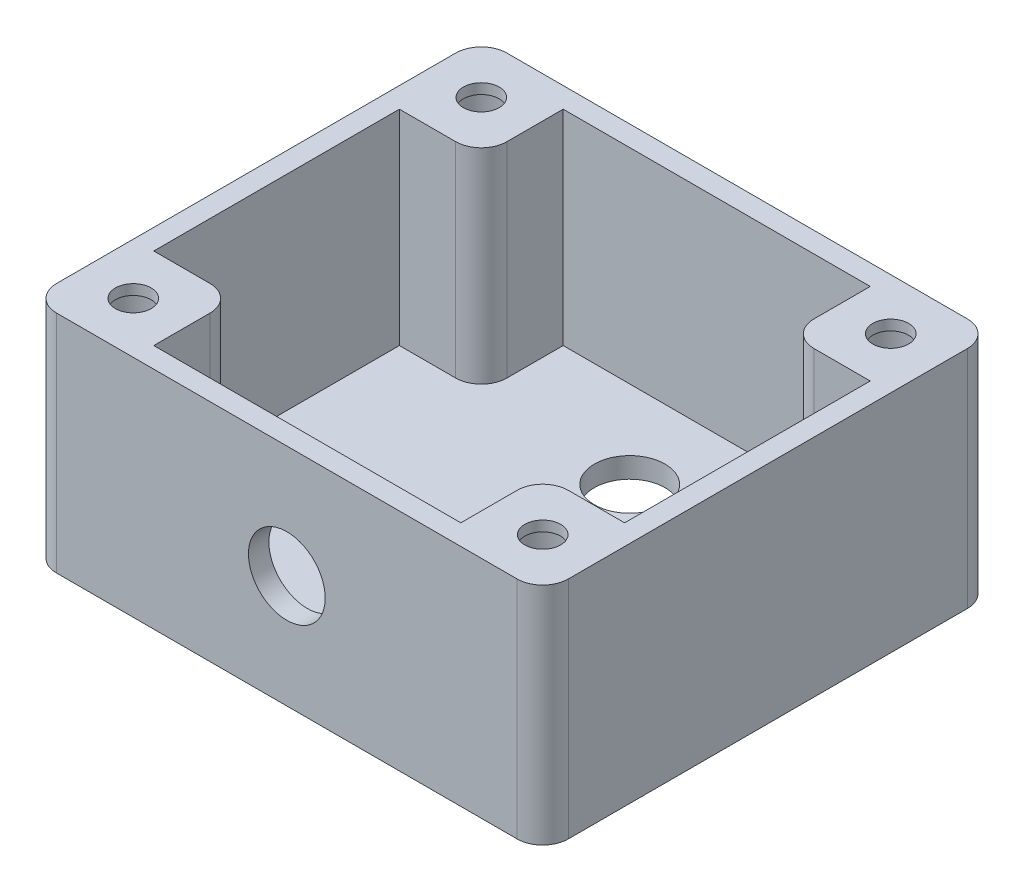
SolidWorks part; units mm, degrees
ref_plane "Front" through (0, 0, 0) normal (0, 0, 1) x (1, 0, 0)
ref_plane "Top" through (0, 0, 0) normal (0, 1, 0) x (1, 0, 0)
ref_plane "Right" through (0, 0, 0) normal (1, 0, 0) x (0, 0, -1)
sketch "Sketch1" plane through (0, 0, 0) normal (0, 1, 0) x (1, 0, 0)
  line L1 (-15, -20) -> (15, -20)
  line L2 (-15, -20) -> (-15, 20)
  line L3 (-15, 20) -> (15, 20)
  line L4 (15, -20) -> (15, 20)
  line L5 (-15, -20) -> (15, 20) construction
  line L6 (-15, 20) -> (15, -20) construction
  line L7 (-25, -22) -> (25, -22)
  line L8 (-25, -22) -> (-25, 22)
  line L9 (-25, 22) -> (25, 22)
  line L10 (25, -22) -> (25, 22)
  line L11 (-25, -22) -> (25, 22) construction
  line L12 (-25, 22) -> (25, -22) construction
  point P0 (0, 0)
  point P6 (0, 0)
  point P7 (0, 0)
  point P8 (0, 0)
  point P10 (0, 0)
  dimension "D5" = 40
  dimension "D6" = 30
  dimension "D7" = 10
  dimension "D8" = 2
extrude "Boss-Extrude4" add sketch "Sketch1" along normal blind 20
sketch "Sketch4" plane through (0, 0, 0) normal (0, -1, 0) x (1, 0, 0)
  line L1 (25, -22) -> (-25, -22)
  line L2 (25, -22) -> (25, 22)
  line L3 (25, 22) -> (-25, 22)
  line L4 (-25, -22) -> (-25, 22)
  line L5 (25, -22) -> (-25, 22) construction
  line L6 (25, 22) -> (-25, -22) construction
  point P0 (0, 0)
extrude "Boss-Extrude5" add sketch "Sketch4" along normal blind 2
sketch "Sketch5" plane through (0, 0, 0) normal (0, 1, 0) x (1, 0, 0)
  line L1 (15, 20) -> (-15, 20) construction
  circle A0 centre (0, 11.5) radius 3.45
  circle A1 centre (8.5, 11.5) radius 1.5
  point P4 (0, 0)
  dimension "D1" = 6.9
  dimension "D3" = 3
  dimension "D2" = 8.5
  dimension "D4" = 8.5
extrude "Cut-Extrude2" cut sketch "Sketch5" against normal blind 2
sketch "Sketch6" plane through (0, 20, 0) normal (0, 1, 0) x (1, 0, 0)
  line L0 (0, 22) -> (0, -22) construction
  line L1 (25, 22) -> (-25, 22) construction
  line L2 (-25, -22) -> (25, -22) construction
  line L3 (-15, -20) -> (-25, -20) construction
  line L4 (-25, 22) -> (-25, -22) construction
  line L5 (-20, -20) -> (-20, 22) construction
  circle A0 centre (-20, 17) radius 1.75
  circle A1 centre (-20, -17) radius 1.75
  dimension "D2" = 3.5
  dimension "D1" = 5
  dimension "D3" = 5
  dimension "D4" = 5
extrude "Cut-Extrude3" cut sketch "Sketch6" against normal through all
mirror "Mirror1" about plane through (0, 0, 0) normal (1, 0, 0) of "Cut-Extrude3"
sketch "Sketch7" plane through (0, -2, 0) normal (0, -1, 0) x (1, 0, 0)
  circle A0 centre (-20, 17) radius 3.25
  circle A1 centre (20, 17) radius 3.25
  circle A2 centre (20, -17) radius 3.25
  circle A3 centre (-20, -17) radius 3.25
  dimension "D1" = 6.5
extrude "Cut-Extrude4" cut sketch "Sketch7" against normal offset from surface (21 mm away) 1 up to face at (20, 20, -15.25)
sketch "Sketch10" plane through (0, 20, 0) normal (0, 1, 0) x (1, 0, 0)
  line L0 (-15, 20) -> (-15, -20) construction
  line L1 (-15, 12) -> (-23, 12)
  line L2 (-15, 12) -> (-15, -12)
  line L3 (-15, -12) -> (-23, -12)
  line L4 (-23, 12) -> (-23, -12)
  line L5 (-25, 22) -> (-25, -22) construction
  line L7 (-25, 22) -> (25, 22) construction
  line L8 (15, 20) -> (-15, 20) construction
  circle A0 centre (-20, 17) radius 1.75 construction
  circle A1 centre (-20, -17) radius 1.75 construction
  dimension "D3" = 5
  dimension "D4" = 5
  dimension "D1" = 2
  dimension "D2" = 2
  dimension "D5" = 5
extrude "Cut-Extrude5" cut sketch "Sketch10" against normal up to surface (20 mm away) up to face at (0, 0, -8.05)
mirror "Mirror2" about plane through (0, 0, 0) normal (1, 0, 0) of "Cut-Extrude5"
sketch "Sketch11" plane through (0, 0, 22) normal (0, 0, 1) x (1, 0, 0)
  line L0 (-25, 9) -> (25, 9) construction
  line L1 (-25, 20) -> (-25, -2) construction
  line L2 (25, 20) -> (25, -2) construction
  circle A0 centre (0, 9) radius 3.75
  point P8 (0, 0)
  point P9 (0, 9)
  dimension "D1" = 7.5
extrude "Cut-Extrude6" cut sketch "Sketch11" against normal up to next
fillet "Fillet1" radius 2.5 8 edges at (-25, 9, 22) (25, 9, 22) (25, 9, -22) (15, 10, 12) (-15, 10, 12) (15, 10, -12) (-15, 10, -12) (-25, 9, -22)
equation "\"D1@Sketch6\"=\"D3@Sketch6\""
equation "\"D4@Sketch6\"=\"D3@Sketch6\""
equation "\"D1@Sketch10\"=\"D2@Sketch10\""
equation "\"D4@Sketch10\"=\"D3@Sketch10\""
equation "\"D5@Sketch10\"=\"D4@Sketch10\""
